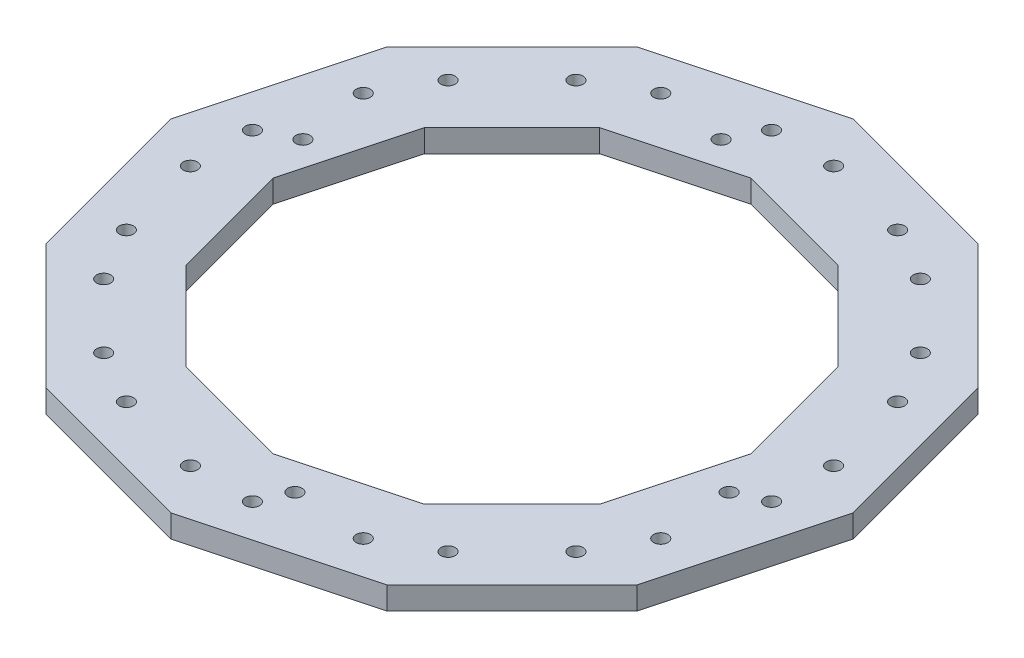
SolidWorks part; units mm, degrees
ref_plane "Front Plane" through (0, 0, 0) normal (0, 0, 1) x (1, 0, 0)
ref_plane "Top Plane" through (0, 0, 0) normal (0, 1, 0) x (1, 0, 0)
ref_plane "Right Plane" through (0, 0, 0) normal (1, 0, 0) x (0, 0, -1)
sketch "Sketch1" plane through (0, 0, 0) normal (0, 1, 0) x (1, 0, 0)
  line L1 (0, 60) -> (-30, 51.9615)
  line L2 (-30, 51.9615) -> (-51.9615, 30)
  line L3 (-51.9615, 30) -> (-60, 0)
  line L4 (-60, 0) -> (-51.9615, -30)
  line L5 (-51.9615, -30) -> (-30, -51.9615)
  line L6 (-30, -51.9615) -> (0, -60)
  line L7 (0, -60) -> (30, -51.9615)
  line L8 (30, -51.9615) -> (51.9615, -30)
  line L9 (51.9615, -30) -> (60, 0)
  line L10 (60, 0) -> (51.9615, 30)
  line L11 (51.9615, 30) -> (30, 51.9615)
  line L12 (30, 51.9615) -> (0, 60)
  circle A0 centre (0, 0) radius 60 construction
  dimension "D1" = 60
extrude "Boss-Extrude1" add sketch "Sketch1" along normal blind 4
sketch "Sketch2" plane through (0, 4, 0) normal (0, 1, 0) x (1, 0, 0)
  line L0 (0, 0) -> (-40.9808, 40.9808) construction
  line L1 (-30, 51.9615) -> (-51.9615, 30) construction
  line L2 (-46.9912, 20.8282) -> (-20.8282, 46.9912) construction
  point P5 (-33.9097, 33.9097)
  dimension "D1" = 10
  dimension "D2" = 37
hole_wizard "Ø2.5mm Dowel Hole1" positions "Sketch6" profile "Sketch5" hole size "Ø2.5" standard "ANSI Metric" end condition through all
sketch "Sketch6" plane through (0, 4, 0) normal (0, 1, 0) x (1, 0, 0)
  point P0 (-46.9912, 20.8282)
  point P3 (-20.8282, 46.9912)
sketch "Sketch5" plane through (-46.9912, 4, -20.8282) normal (1, 0, 0) x (0, 0, 1)
  line L0 (0, 0) -> (0, 4)
  line L1 (0, 4) -> (1.25, 4)
  line L2 (1.25, 4) -> (1.25, 0)
  line L5 (1.25, 0) -> (0, 0)
  line L11 (0, -6.35) -> (0, 107.95) construction
  dimension "Thru Hole Dia." = 2.5
  dimension "Thru Hole Depth" = 4
ref_axis "Axis1" through (0, 4, 0) along (0, 1, 0)
pattern_circular "CirPattern2" count 12 over 360 about axis through (0, 4, 0) along (0, 1, 0) of "Ø2.5mm Dowel Hole1"
sketch "Sketch7" plane through (0, 4, 0) normal (0, 1, 0) x (1, 0, 0)
  line L0 (-40.9808, 40.9808) -> (40.9808, -40.9808) construction
  line L1 (30, -51.9615) -> (51.9615, -30) construction
  line L2 (26.8701, -26.8701) -> (-26.8701, 26.8701)
  line L3 (-8.4853, 45.2548) -> (-45.2548, 8.4853) construction
  line L4 (7.7782, -45.9619) -> (45.9619, -7.7782) construction
  dimension "D1" = 76
  dimension "D2" = 54
  dimension "D3" = 52
hole_wizard "Ø2.5mm Dowel Hole2" positions "Sketch9" profile "Sketch8" hole size "Ø2.5" standard "ANSI Metric" end condition through all
sketch "Sketch9" plane through (0, 4, 0) normal (0, 1, 0) x (1, 0, 0)
  point P0 (-45.2548, 8.4853)
  point P3 (-8.4853, 45.2548)
  point P6 (45.9619, -7.7782)
  point P9 (7.7782, -45.9619)
sketch "Sketch8" plane through (-45.2548, 4, -8.4853) normal (1, 0, 0) x (0, 0, 1)
  line L0 (0, 0) -> (0, 4)
  line L1 (0, 4) -> (1.25, 4)
  line L2 (1.25, 4) -> (1.25, 0)
  line L5 (1.25, 0) -> (0, 0)
  line L11 (0, -6.35) -> (0, 107.95) construction
  dimension "Thru Hole Dia." = 2.5
  dimension "Thru Hole Depth" = 4
sketch "Sketch10" plane through (0, 4, 0) normal (0, 1, 0) x (1, 0, 0)
  line L0 (-30, 51.9615) -> (-51.9615, 30) construction
  line L1 (0, 42) -> (-21, 36.3731)
  line L2 (-21, 36.3731) -> (-36.3731, 21)
  line L3 (-36.3731, 21) -> (-42, 0)
  line L4 (-42, 0) -> (-36.3731, -21)
  line L5 (-36.3731, -21) -> (-21, -36.3731)
  line L6 (-21, -36.3731) -> (0, -42)
  line L7 (0, -42) -> (21, -36.3731)
  line L8 (21, -36.3731) -> (36.3731, -21)
  line L9 (36.3731, -21) -> (42, 0)
  line L10 (42, 0) -> (36.3731, 21)
  line L11 (36.3731, 21) -> (21, 36.3731)
  line L12 (21, 36.3731) -> (0, 42)
  circle A0 centre (0, 0) radius 40.5689 construction
  dimension "D1" = 42
extrude "Cut-Extrude1" cut sketch "Sketch10" against normal through all
